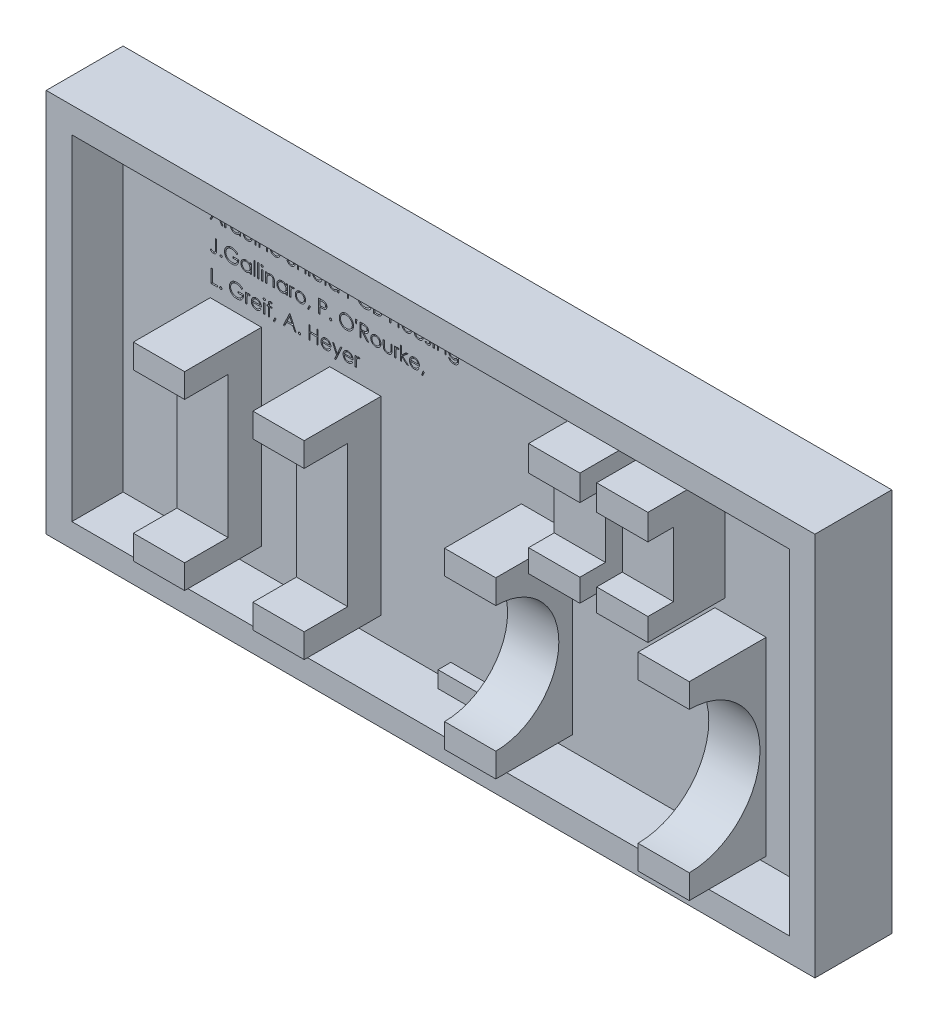
SolidWorks part; units mm, degrees
ref_plane "Front Plane" through (0, 0, 0) normal (0, 0, 1) x (1, 0, 0)
ref_plane "Top Plane" through (0, 0, 0) normal (0, 1, 0) x (1, 0, 0)
ref_plane "Right Plane" through (0, 0, 0) normal (1, 0, 0) x (0, 0, -1)
sketch "Sketch3" plane through (0, 0, 0) normal (0, 0, 1) x (1, 0, 0)
  line L5 (0, 0) -> (150, 0)
  line L6 (0, 0) -> (0, 75)
  line L7 (0, 75) -> (150, 75)
  line L8 (150, 0) -> (150, 75)
  dimension "D1" = 150
  dimension "D2" = 75
extrude "Boss-Extrude1" add sketch "Sketch3" along normal blind 5
sketch "Sketch5" plane through (0, 0, 5) normal (0, 0, 1) x (1, 0, 0)
  line L0 (0, 74.6253) -> (150, 0)
  line L1 (0, -2.75) -> (0, 2.75) construction
  line L2 (2.75, 0) -> (-2.75, 0) construction
  line L3 (150, 0) -> (150, 75) construction
  line L4 (0, 0) -> (150, 75)
  line L5 (150, 75) -> (0, 75) construction
  line L6 (5, 4.6253) -> (145, 4.6253)
  line L7 (5, 4.6253) -> (5, 70)
  line L8 (5, 70) -> (145, 70)
  line L9 (145, 4.6253) -> (145, 70)
  line L10 (5, 4.6253) -> (145, 70) construction
  line L11 (5, 70) -> (145, 4.6253) construction
  line L13 (0, -0.3747) -> (150, -0.3747)
  line L14 (0, -0.3747) -> (0, 75)
  line L15 (0, 75) -> (150, 75)
  line L16 (150, -0.3747) -> (150, 75)
  line L17 (0, -0.3747) -> (150, 75) construction
  line L18 (0, 75) -> (150, -0.3747) construction
  point P12 (75, 37.3127)
  point P19 (75, 37.3127)
  line M5 (0, 75) -> (0, 0)
  line M6 (0, 0) -> (150, 0)
  line M7 (150, 0) -> (150, 75)
  line M8 (150, 75) -> (0, 75)
  dimension "D1" = 5
  dimension "D2" = 5
extrude "Boss-Extrude2" add sketch "Sketch5" along normal blind 10 contours L7 L8 L0 L4 L6 M5 | L0 L8 L4 M8 M5 | L9 L6 L0 L4 L8 M7 | L6 L4 L0 M6 region at (74.6507, 72.5589, 5) region at (2.5686, 37.3226, 5) region at (74.9886, 2.2619, 5) region at (147.4097, 37.6418, 5)
sketch "Sketch8" plane through (0, 0, 5) normal (0, 0, 1) x (1, 0, 0)
  line L0 (45.3337, 45.9696) -> (55.3337, 45.9696)
  line L1 (99.1303, 67.3917) -> (109.1303, 67.3917)
  line L2 (99.1303, 67.3917) -> (99.1303, 45.3917)
  line L3 (99.1303, 45.3917) -> (109.1303, 45.3917)
  line L4 (109.1303, 67.3917) -> (109.1303, 45.3917)
  line L5 (120.4868, 42.8214) -> (130.4868, 42.8214)
  line L6 (120.4868, 42.8214) -> (120.4868, 5.8214)
  line L7 (120.4868, 5.8214) -> (130.4868, 5.8214)
  line L8 (130.4868, 42.8214) -> (130.4868, 5.8214)
  line L9 (82.7278, 41.4938) -> (92.7278, 41.4938)
  line L10 (82.7278, 41.4938) -> (82.7278, 7.4938)
  line L11 (82.7278, 7.4938) -> (92.7278, 7.4938)
  line L12 (92.7278, 41.4938) -> (92.7278, 7.4938)
  line L13 (22.0055, 45.9696) -> (32.0055, 45.9696)
  line L14 (22.0055, 45.9696) -> (22.0055, 8.9696)
  line L15 (22.0055, 8.9696) -> (32.0055, 8.9696)
  line L16 (32.0055, 45.9696) -> (32.0055, 8.9696)
  line L17 (45.3337, 45.9696) -> (45.3337, 8.9696)
  line L18 (45.3337, 8.9696) -> (55.3337, 8.9696)
  line L19 (55.3337, 45.9696) -> (55.3337, 8.9696)
  line L20 (112.4087, 67.3917) -> (122.4087, 67.3917)
  line L21 (112.4087, 67.3917) -> (112.4087, 45.3917)
  line L22 (112.4087, 45.3917) -> (122.4087, 45.3917)
  line L23 (122.4087, 67.3917) -> (122.4087, 45.3917)
  dimension "D1" = 22
  dimension "D2" = 10
  dimension "D3" = 37
  dimension "D4" = 10
  dimension "D5" = 34
  dimension "D6" = 10
  dimension "D7" = 37
  dimension "D8" = 10
extrude "Boss-Extrude3" add sketch "Sketch8" along normal blind 15
sketch "Sketch10" plane through (122.4087, 0, 0) normal (1, 0, 0) x (0, 0, -1)
  line L0 (-20, 45.3917) -> (-20, 67.3917) construction
  line L1 (-20, 62.3917) -> (-15, 62.3917)
  line L2 (-20, 62.3917) -> (-20, 49.7917)
  line L3 (-20, 49.7917) -> (-15, 49.7917)
  line L5 (-20, 67.3917) -> (-20, 62.3917)
  line L6 (-15, 62.3917) -> (-15, 49.7917)
  line L7 (-20, 67.3917) -> (-5, 67.3917) construction
  line L8 (-20, 49.7917) -> (-20, 45.3917)
  line M8 (-20, 67.3917) -> (-20, 45.3917)
  dimension "D1" = 12.6
  dimension "D2" = 5
  dimension "D3" = 5
  dimension "D4" = 4.4
extrude "Cut-Extrude1" cut sketch "Sketch10" against normal blind 25 contours L6 L1 L3 M8 region at (122.4087, 56.0917, 17.5)
sketch "Sketch11" plane through (130.4868, 0, 0) normal (1, 0, 0) x (0, 0, -1)
  line L0 (-20, 5.8214) -> (-20, 42.8214) construction
  circle A0 centre (-20, 24.3214) radius 13.8
  dimension "D1" = 27.6
extrude "Cut-Extrude2" cut sketch "Sketch11" against normal blind 25
sketch "Sketch12" plane through (92.7278, 0, 0) normal (1, 0, 0) x (0, 0, -1)
  line L0 (-20, 7.4938) -> (-20, 41.4938) construction
  circle A0 centre (-20, 24.4938) radius 12.3
  dimension "D1" = 24.6
extrude "Cut-Extrude3" cut sketch "Sketch12" against normal blind 25
sketch "Sketch13" plane through (55.3337, 0, 0) normal (1, 0, 0) x (0, 0, -1)
  line L0 (-20, 27.4696) -> (-20, 41.2696)
  line L1 (-20, 8.9696) -> (-20, 45.9696) construction
  line L2 (-20, 41.2696) -> (-11.5, 41.2696)
  line L3 (-20, 27.4696) -> (-20, 13.6696)
  line L5 (-11.5, 41.2696) -> (-11.5, 13.6696)
  line L6 (-11.5, 13.6696) -> (-20, 13.6696)
  dimension "D1" = 13.8
  dimension "D2" = 13.8
  dimension "D3" = 8.5
extrude "Cut-Extrude4" cut sketch "Sketch13" against normal blind 36
sketch "Sketch14" plane through (0, 0, 0) normal (0, 0, -1) x (-1, 0, 0)
  line L3 (-77.8, 0) -> (-72.2, 0)
  line L15 (-80.3, 7.8) -> (-80.3, 2.2)
  line L17 (-69.7, 7.8) -> (-69.7, 2.2)
  line L18 (-80.3, 2.2) -> (-77.8, 2.2)
  line L19 (-72.2, 2.2) -> (-69.7, 2.2)
  line L21 (-77.8, 0) -> (-77.8, 2.2)
  line L23 (-80.3, 7.8) -> (-69.7, 7.8)
  line L25 (-72.2, 0) -> (-72.2, 2.2)
extrude "Cut-Extrude5" cut sketch "Sketch14" against normal blind 5
sketch "Sketch15" plane through (0, 4.6253, 0) normal (0, 1, 0) x (1, 0, 0)
  line L6 (5, -5) -> (69.7, -5) construction
  line L11 (68.9567, -5) -> (80.9567, -5)
  line L12 (68.9567, -5) -> (68.9567, -7.5)
  line L13 (68.9567, -7.5) -> (80.9567, -7.5)
  line L14 (80.9567, -5) -> (80.9567, -7.5)
  dimension "D1" = 12
  dimension "D2" = 2.5
extrude "Boss-Extrude11" add sketch "Sketch15" along normal blind 3.2
sketch "Sketch19" plane through (0, 0, 5) normal (0, 0, 1) x (1, 0, 0)
  text T0 "Introduction to Soft Robotics\r\nArduino Shield PCB Housing\r\nJ.Gallinaro, P. O'Rourke, \r\nL. Greif, A. Heyer" font "Century Gothic" height in points 10
extrude "Cut-Extrude6" cut sketch "Sketch19" against normal blind 1
